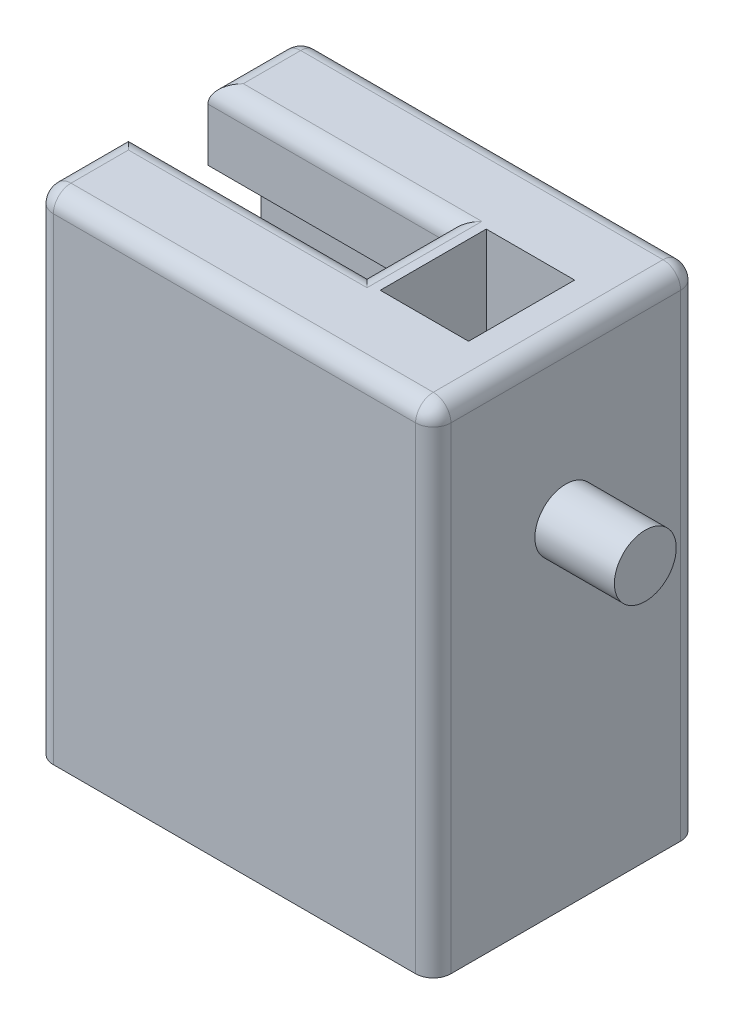
SolidWorks part; units mm, degrees
ref_plane "Plan de face" through (0, 0, 0) normal (0, 0, 1) x (1, 0, 0)
ref_plane "Plan de dessus" through (0, 0, 0) normal (0, 1, 0) x (1, 0, 0)
ref_plane "Plan de droite" through (0, 0, 0) normal (1, 0, 0) x (0, 0, -1)
sketch "Esquisse1" plane through (0, 0, 0) normal (0, 1, 0) x (1, 0, 0)
  line L0 (0, 0) -> (0, 15) construction
  line L1 (0, 0) -> (57, 0) construction
  line L2 (6, 15) -> (6, -15) construction
  line L3 (-16.5, -15) -> (28.5, -15)
  line L4 (-16.5, -15) -> (-16.5, 15)
  line L5 (-16.5, 15) -> (28.5, 15)
  line L6 (28.5, -15) -> (28.5, 15)
  point P8 (28.5, 0)
  dimension "D1" = 30
  dimension "D2" = 45
  dimension "D3" = 6
extrude "Boss.-Extru.1" add sketch "Esquisse1" along normal blind 8
sketch "Esquisse5" plane through (-16.5, 0, 0) normal (-1, 0, 0) x (0, 0, 1)
  line L0 (-15, 8) -> (-15, 56)
  line L1 (-15, 56) -> (15, 56)
  line L2 (15, 56) -> (15, 8)
  line L3 (-15, 8) -> (15, 8)
  dimension "D1" = 48
extrude "Boss.-Extru.3" add sketch "Esquisse5" against normal up to surface (45 mm away) up to face at (28.5, 4, 0)
sketch "Esquisse6" plane through (-16.5, 0, 0) normal (-1, 0, 0) x (0, 0, 1)
  line L2 (10.5, 48) -> (4.5, 48)
  line L3 (-10.5, 48) -> (-10.5, 8)
  line L4 (-10.5, 8) -> (10.5, 8)
  line L5 (10.5, 8) -> (10.5, 48)
  line L6 (0, 0) -> (0, 56) construction
  line L7 (-15, 0) -> (15, 0) construction
  line L8 (15, 56) -> (-15, 56) construction
  line L9 (-15, 28) -> (15, 28) construction
  line L10 (-15, 56) -> (-15, 0) construction
  line L11 (15, 56) -> (15, 0) construction
  line L12 (4.5, 48) -> (4.5, 56)
  line L13 (4.5, 56) -> (-4.5, 56)
  line L14 (-4.5, 56) -> (-4.5, 48)
  line L15 (-4.5, 48) -> (-10.5, 48)
  point P11 (0, 8)
  point P20 (0, 28)
  point P25 (0, 56)
  dimension "D1" = 21
  dimension "D2" = 9
  dimension "D3" = 40
  dimension "D4" = 8
extrude "Enlèv. mat.-Extru.1" cut sketch "Esquisse6" against normal blind 27 contours L2 L12 L13 L14 L15 L3 L4 L5
sketch "Esquisse7" plane through (-16.5, 0, 0) normal (-1, 0, 0) x (0, 0, 1)
  line L0 (0, 0) -> (0, 8) construction
  line L1 (-15, 0) -> (15, 0) construction
  line L2 (-10.5, 8) -> (10.5, 8) construction
  line L3 (-5, 4) -> (5, 4) construction
  circle A0 centre (-5, 4) radius 1.3509
  circle A1 centre (5, 4) radius 1.3509
  dimension "D1" = 10
  dimension "D2" = 4
sketch "Esquisse16" plane through (28.5, 0, 0) normal (1, 0, 0) x (0, 0, -1)
  line L0 (0, 0) -> (0, 56) construction
  line L1 (-15, 0) -> (15, 0) construction
  line L2 (15, 56) -> (-15, 56) construction
  circle A0 centre (0, 38) radius 3.5
  dimension "D1" = 7
  dimension "D2" = 18
fillet "Congé1" radius 2 12 edges at (28.5, 28, 15) (28.5, 28, -15) (-16.5, 28, 15) (-16.5, 28, -15) (-16.5, 56, -9.75) (-16.5, 56, 9.75) (6, 56, -15) (6, 56, 15) (28.5, 56, 0) (-3, 56, 4.5) (10.5, 56, 0) (-3, 56, -4.5)
extrude "Boss.-Extru.5" add sketch "Esquisse16" along normal blind 9
ref_axis "Axe2" through (0, 52.2109, 0) along (0, -1, 0)
sketch "Esquisse21" plane through (0, 8, 0) normal (0, 1, 0) x (1, 0, 0)
  line L0 (0, 0) -> (0, 23.8533) construction
  line L1 (-7.5, 0) -> (7.5, 0) construction
  point P6 (0, 0)
  dimension "D1" = 15
hole_wizard "Dégagement M32" positions "Esquisse22" profile "Esquisse23" hole size "M3" standard "ISO" end condition through all
sketch "Esquisse22" plane through (0, 8, 0) normal (0, 1, 0) x (1, 0, 0)
  point P0 (-7.5, 0)
  point P3 (7.5, 0)
sketch "Esquisse23" plane through (-7.5, 8, 0) normal (1, 0, 0) x (0, 0, 1)
  line L0 (0, 0) -> (0, 8)
  line L1 (0, 8) -> (1.6, 8)
  line L2 (1.6, 8) -> (1.6, 0)
  line L5 (1.6, 0) -> (0, 0)
  line L11 (0, -6.35) -> (0, 107.95) construction
  dimension "Diamètre du perçage jusqu'au prochain" = 3.2
  dimension "Profondeur du perçage jusqu'au prochain" = 8
ref_axis "Axe3" through (51.1437, 38, 0) along (-1, 0, 0)
sketch "Esquisse24" plane through (-16.5, 0, 0) normal (-1, 0, 0) x (0, 0, 1)
  line L0 (0, 0) -> (0, 8) construction
  line L1 (-13, 0) -> (13, 0) construction
  line L2 (-10.5, 8) -> (10.5, 8) construction
  circle A0 centre (-5, 3.5) radius 2.4931
  circle A1 centre (5, 3.5) radius 2.4931
  point P10 (5.807, 3.925)
  dimension "D1" = 4.5
  dimension "D2" = 10
hole_wizard "Dégagement M33" positions "Esquisse25" profile "Esquisse27" hole size "M3" standard "ISO"
sketch "Esquisse25" plane through (-16.5, 0, 0) normal (-1, 0, 0) x (0, 0, 1)
  point P0 (-5, 3.5)
  point P3 (5, 3.5)
sketch "Esquisse27" plane through (-16.5, 3.5, -5) normal (0, 1, 0) x (0, 0, 1)
  line L0 (0, 0) -> (0, 8.9614)
  line L1 (0, 8.9614) -> (1.6, 8)
  line L2 (1.6, 8) -> (1.6, 0)
  line L5 (1.6, 0) -> (0, 0)
  line L10 (0, 8.9614) -> (-1.6, 8) construction
  line L11 (0, -6.35) -> (0, 107.95) construction
  dimension "Diamètre du perçage" = 3.2
  dimension "Profondeur du perçage" = 8
  dimension "Angle de pointe" = 118
sketch "Esquisse28" plane through (0, 56, 0) normal (0, 1, 0) x (1, 0, 0)
  line L0 (0, 0) -> (13.5, 0) construction
  line L2 (23.5, 6) -> (13.5, 6)
  line L3 (23.5, 6) -> (23.5, -6)
  line L4 (23.5, -6) -> (13.5, -6)
  line L5 (13.5, 6) -> (13.5, -6)
  line L6 (23.5, 6) -> (13.5, -6) construction
  line L7 (23.5, -6) -> (13.5, 6) construction
  point P3 (18.5, 0)
  point P8 (13.4721, 0)
  point P9 (14.5979, 0)
  dimension "D1" = 13.5
  dimension "D2" = 10
  dimension "D3" = 12
extrude "Enlèv. mat.-Extru.2" cut sketch "Esquisse28" against normal through all
equation "\"!.00mm\"=40"
